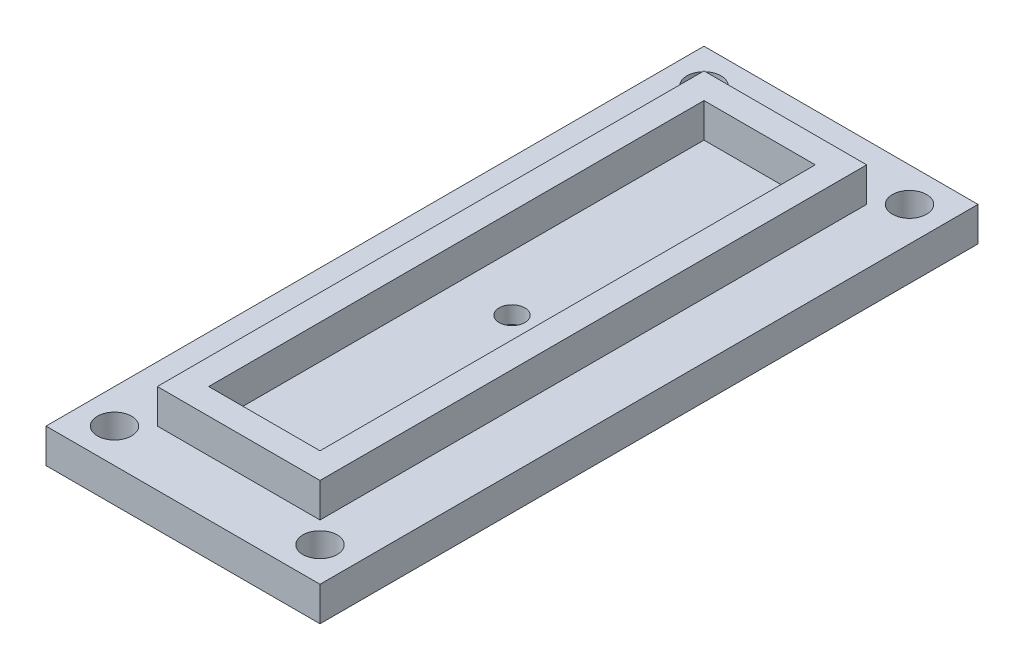
SolidWorks part; units mm, degrees
material "ABS"
ref_plane "Front Plane" through (0, 0, 0) normal (0, 0, 1) x (1, 0, 0)
ref_plane "Top Plane" through (0, 0, 0) normal (0, 1, 0) x (1, 0, 0)
ref_plane "Right Plane" through (0, 0, 0) normal (1, 0, 0) x (0, 0, -1)
sketch "Sketch1" plane through (0, 0, 0) normal (0, 1, 0) x (1, 0, 0)
  line L0 (-8, 19.21) -> (8, 19.21) construction
  line L1 (-8, -19.21) -> (8, -19.21)
  line L2 (-8, -19.21) -> (-8, 19.21)
  line L3 (-8, 19.21) -> (8, 19.21)
  line L4 (8, -19.21) -> (8, 19.21)
  line L5 (-8, -19.21) -> (8, 19.21) construction
  line L6 (-8, 19.21) -> (8, -19.21) construction
  line L7 (8, 19.21) -> (8, -19.21) construction
  point P0 (0, 0)
extrude "Boss-Extrude1" add sketch "Sketch1" along normal blind 2
sketch "Sketch2" plane through (0, 2, 0) normal (0, 1, 0) x (1, 0, 0)
  line L1 (-4, -15.21) -> (4, -15.21)
  line L2 (-4, -15.21) -> (-4, 15.21)
  line L3 (-4, 15.21) -> (4, 15.21)
  line L4 (4, -15.21) -> (4, 15.21)
  line L5 (-4, -15.21) -> (4, 15.21) construction
  line L6 (-4, 15.21) -> (4, -15.21) construction
  point P0 (0, 0)
extrude "Extrude-Thin1" add sketch "Sketch2" along normal blind 2 thin thin type mid plane wall 1.5
sketch "Sketch3" plane through (0, 0, 0) normal (0, -1, 0) x (1, 0, 0)
  line L1 (8, 19.21) -> (8, -19.21) construction
  circle A0 centre (6, 17.21) radius 1
  dimension "D1" = 2
  dimension "D2" = 2
extrude "Cut-Extrude1" cut sketch "Sketch3" against normal through all
sketch "Sketch4" plane through (0, 2, 0) normal (0, 1, 0) x (1, 0, 0)
  line L0 (4.75, 0) -> (-4.75, 0) construction
  line L1 (4.75, -15.96) -> (4.75, 15.96) construction
  line L2 (-4.75, 15.96) -> (-4.75, -15.96) construction
  line L3 (0, 14.46) -> (0, -14.46) construction
  line L4 (3.25, 14.46) -> (-3.25, 14.46) construction
  line L5 (-3.25, -14.46) -> (3.25, -14.46) construction
ref_plane "Plane1" through (0, 0, 0) normal (-1, 0, 0) x (0, 0, 1)
ref_plane "Plane2" through (0, 0, 0) normal (0, 0, -1) x (-1, 0, 0)
mirror "Mirror1" about plane through (0, 0, 0) normal (0, 0, -1) of "Cut-Extrude1"
mirror "Mirror2" about plane through (0, 0, 0) normal (-1, 0, 0) of "Mirror1"
extrude "Cut-Extrude-Thin1" cut sketch "Sketch2<3>" against normal blind 2 from offset 1 thin offset against normal yes thin type mid plane wall 1.5
sketch "Sketch2<3>" plane through (0, 2, 0) normal (0, 1, 0) x (1, 0, 0) same geometry as "Sketch2"
sketch "Sketch5" plane through (0, 2, 0) normal (0, 1, 0) x (1, 0, 0)
  circle A0 centre (0, 0) radius 0.75
  dimension "D1" = 1.5
extrude "Cut-Extrude2" cut sketch "Sketch5" against normal through all and the other way through all
sketch "Sketch6" plane through (0, 0, 0) normal (0, -1, 0) x (1, 0, 0)
  circle A0 centre (0, 0) radius 1.25
  dimension "D1" = 2.5
extrude "Cut-Extrude3" cut sketch "Sketch6" against normal blind 1
